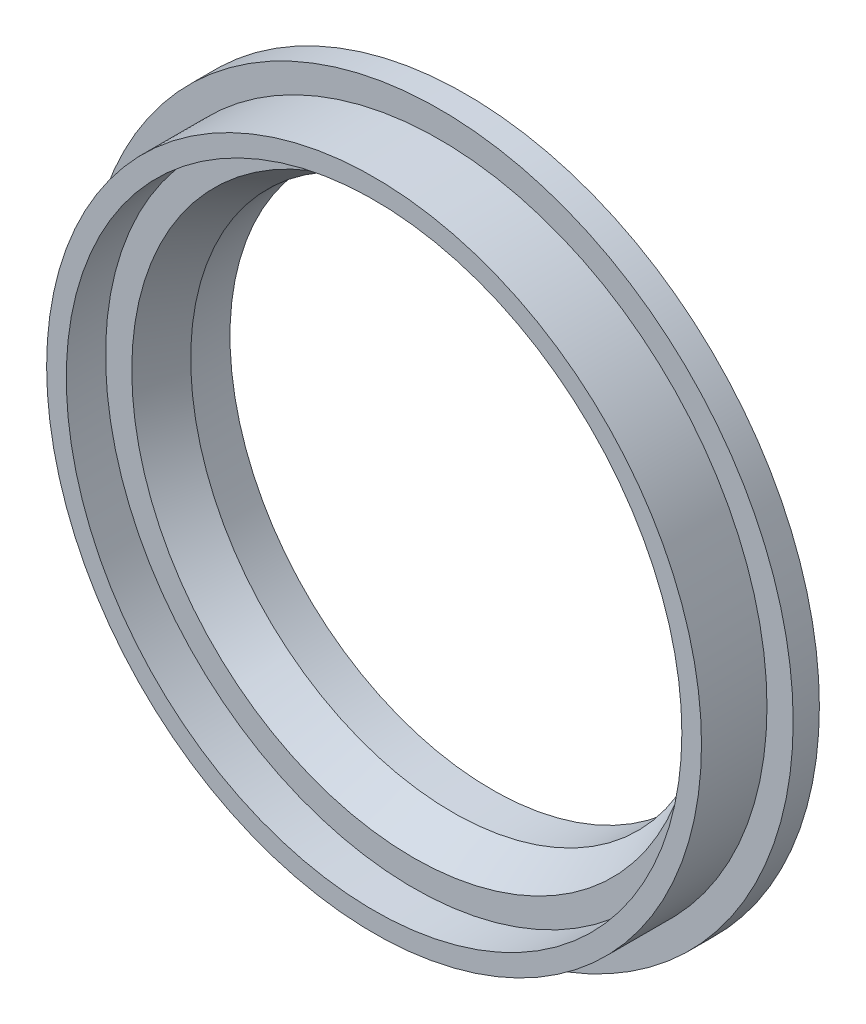
SolidWorks part; units mm, degrees
material "ABS"
ref_plane "Front" through (0, 0, 0) normal (0, 0, 1) x (1, 0, 0)
ref_plane "Top" through (0, 0, 0) normal (0, 1, 0) x (1, 0, 0)
ref_plane "Right" through (0, 0, 0) normal (1, 0, 0) x (0, 0, -1)
sketch "Szkic1" plane through (0, 0, 0) normal (0, 1, 0) x (1, 0, 0)
  line L1 (20, 9.5) -> (20, 6.5)
  line L2 (27, 7.5) -> (27, 5.5)
  line L3 (25, 5.5) -> (25, 0.5)
  line L4 (20, 9.5) -> (23, 9.5)
  line L5 (23.5, 3.5) -> (21.5, 3.5)
  line L6 (23, 8.5) -> (27, 7.5)
  line L7 (23, 9.5) -> (23, 8.5)
  line L8 (23.5, 0.5) -> (23.5, 3.5)
  line L9 (27, 5.5) -> (25, 5.5)
  line L10 (20, 6.5) -> (21.5, 3.5)
  line L11 (25, 0.5) -> (23.5, 0.5)
  line L12 (0, 0) -> (0, 19.6753) construction
revolve "Obrót1" add sketch "Szkic1" angle 360 about L12
